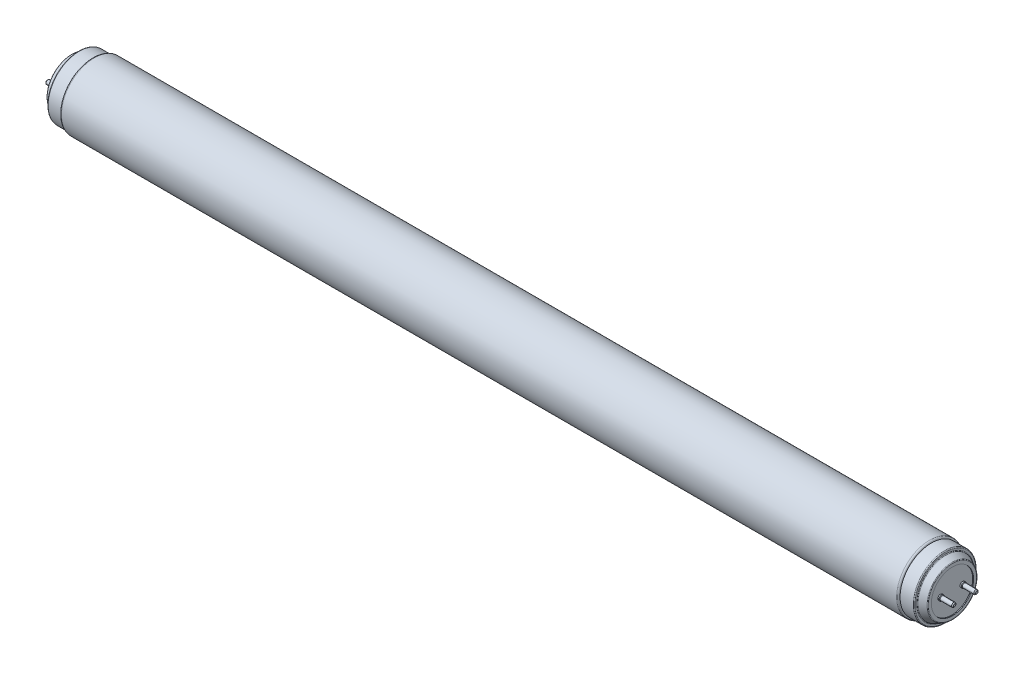
SolidWorks part; units mm, degrees
ref_plane "Front Plane" through (0, 0, 0) normal (0, 0, 1) x (1, 0, 0)
ref_plane "Top Plane" through (0, 0, 0) normal (0, 1, 0) x (1, 0, 0)
ref_plane "Right Plane" through (0, 0, 0) normal (1, 0, 0) x (0, 0, -1)
sketch "Sketch1" plane through (0, 0, 0) normal (0, 0, 1) x (1, 0, 0)
  line L0 (0, -17.75) -> (-7.5, -17.75)
  line L1 (-8, -17.25) -> (-8, -16.309)
  line L2 (-8.2764, -15.8618) -> (-11.7236, -14.1382)
  line L3 (-12, -13.691) -> (-12, -12)
  line L4 (-12, -12) -> (-11.5, -12)
  line L5 (-11.5, -12) -> (-11.5, 0)
  line L6 (-11.5, 0) -> (0, 0)
  line L7 (0, 0) -> (0, -17.75) construction
  line L8 (0.95, -18.7) -> (475.05, -18.7)
  line L9 (238, -18.7) -> (238, 0) construction
  line L10 (0, 0) -> (476, 0)
  line L11 (476, 0) -> (476, -17.75) construction
  line L12 (487.5, 0) -> (476, 0)
  line L13 (487.5, -12) -> (487.5, 0)
  line L14 (488, -12) -> (487.5, -12)
  line L15 (488, -13.691) -> (488, -12)
  line L16 (484.2764, -15.8618) -> (487.7236, -14.1382)
  line L17 (484, -17.25) -> (484, -16.309)
  line L18 (476, -17.75) -> (483.5, -17.75)
  line L19 (-11.5, 0) -> (-47.7314, 0) construction
  arc A0 (0, -17.75) -> (0.95, -18.7) centre (0.95, -17.75) ccw
  arc A1 (-7.5, -17.75) -> (-8, -17.25) centre (-7.5, -17.25) cw
  arc A2 (-8, -16.309) -> (-8.2764, -15.8618) centre (-8.5, -16.309) ccw
  arc A3 (-11.7236, -14.1382) -> (-12, -13.691) centre (-11.5, -13.691) cw
  arc A4 (487.7236, -14.1382) -> (488, -13.691) centre (487.5, -13.691) ccw
  arc A5 (484, -16.309) -> (484.2764, -15.8618) centre (484.5, -16.309) cw
  arc A6 (483.5, -17.75) -> (484, -17.25) centre (483.5, -17.25) ccw
  arc A7 (476, -17.75) -> (475.05, -18.7) centre (475.05, -17.75) cw
  point P15 (-8, -17.75)
  point P18 (-8, -16)
  point P21 (-12, -14)
  point P38 (488, -14)
  point P39 (484, -16)
  point P40 (484, -17.75)
  dimension "D9" = 0.5
  dimension "D1" = 17.75
  dimension "D2" = 8
  dimension "D3" = 14
  dimension "D4" = 12
  dimension "D5" = 0.5
  dimension "D6" = 12
  dimension "D7" = 16
  dimension "D8" = 18.7
  dimension "D10" = 500
revolve "Revolve1" add sketch "Sketch1" angle 360 about L19
sketch "Sketch2" plane through (-11.5, 0, 0) normal (-1, 0, 0) x (0, 0, 1)
  line L0 (-6.3, 0) -> (6.3, 0) construction
  circle A0 centre (-6.3, 0) radius 1.2
  circle A1 centre (6.3, 0) radius 1.2
  dimension "D1" = 2.4
  dimension "D2" = 15
extrude "Extrude1" add sketch "Sketch2" along normal blind 8
sketch "Sketch3" plane through (-11.5, 0, 0) normal (-1, 0, 0) x (0, 0, 1)
  circle A0 centre (-6.3, 0) radius 1.5
  circle A1 centre (6.3, 0) radius 1.5
  dimension "D1" = 3
  dimension "D2" = 3
extrude "Extrude2" add sketch "Sketch3" along normal blind 1
sketch "Sketch4" plane through (487.5, 0, 0) normal (1, 0, 0) x (0, 0, -1)
  circle A0 centre (6.3, 0) radius 1.2 construction
  circle A1 centre (-6.3, 0) radius 1.2 construction
  circle A2 centre (6.3, 0) radius 1.2
  circle A3 centre (-6.3, 0) radius 1.2
extrude "Extrude3" add sketch "Sketch4" along normal blind 8
sketch "Sketch5" plane through (487.5, 0, 0) normal (1, 0, 0) x (0, 0, -1)
  circle A0 centre (6.3, 0) radius 1.5 construction
  circle A1 centre (-6.3, 0) radius 1.5 construction
  circle A2 centre (6.3, 0) radius 1.5
  circle A3 centre (-6.3, 0) radius 1.5
extrude "Extrude4" add sketch "Sketch5" along normal blind 1
chamfer "Chamfer1" distance 0.3 angle 45 4 edges at (-12.5, 0, 7.8) (-12.5, 0, -4.8) (488.5, 0, -7.8) (488.5, 0, 4.8)
chamfer "Chamfer2" distance 0.5 angle 45 4 edges at (-19.5, 0, -5.1) (-19.5, 0, 7.5) (495.5, 0, -7.5) (495.5, 0, 5.1)
